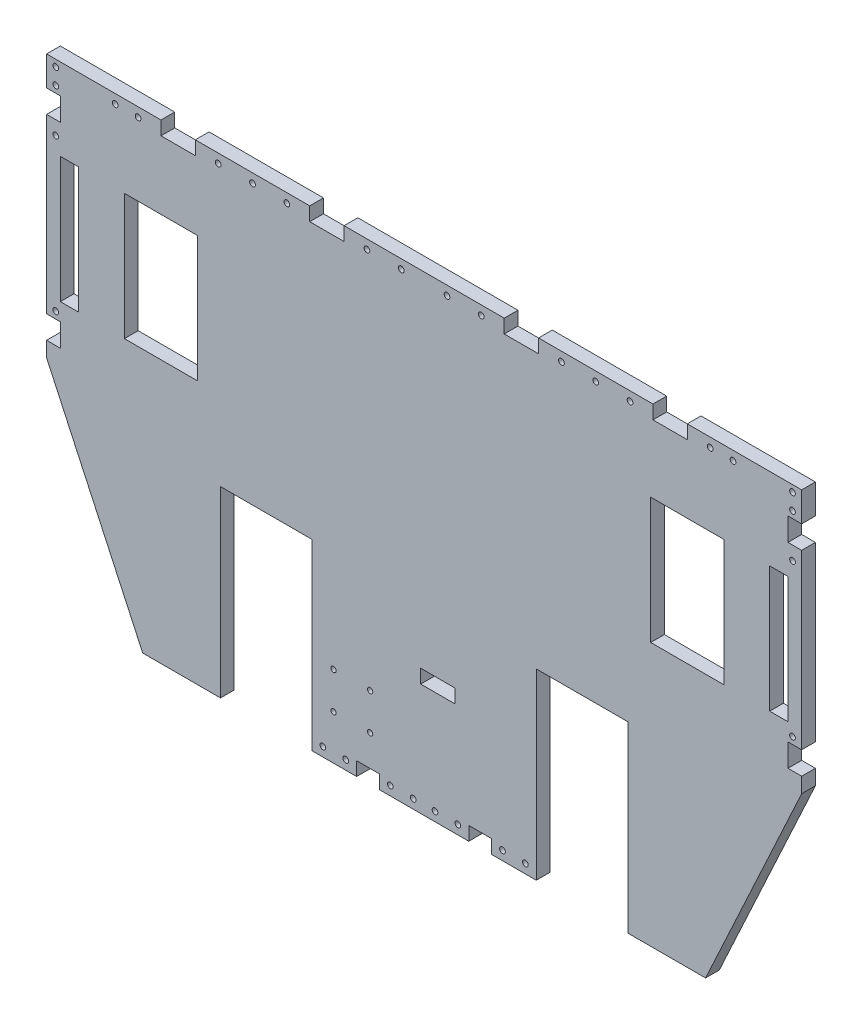
SolidWorks part; units mm, degrees
ref_plane "Plan de face" through (0, 0, 0) normal (0, 0, 1) x (1, 0, 0)
ref_plane "Plan de dessus" through (0, 0, 0) normal (0, 1, 0) x (1, 0, 0)
ref_plane "Plan de droite" through (0, 0, 0) normal (1, 0, 0) x (0, 0, -1)
sketch "Esquisse1" plane through (0, 0, 0) normal (0, 0, 1) x (1, 0, 0)
  line L0 (0, 124.9429) -> (0, -204.46) construction
  line L1 (-165, 96.73) -> (165, 96.73)
  line L2 (165, 96.73) -> (165, -18.27)
  line L3 (165, -18.27) -> (123, -109.0224)
  line L4 (123, -109.0224) -> (-123, -109.0224)
  line L5 (-211.9802, 0) -> (248.5953, 0) construction
  line L6 (-123, -109.0224) -> (-165, -18.27)
  line L7 (-165, -18.27) -> (-165, 96.73)
  line L9 (13.5, -54.0224) -> (-1.5, -54.0224)
  line L10 (13.5, -54.0224) -> (13.5, -60.0224)
  line L11 (13.5, -60.0224) -> (-1.5, -60.0224)
  line L12 (-1.5, -54.0224) -> (-1.5, -60.0224)
  circle A0 centre (-23.6, -89.5224) radius 1.15
  circle A1 centre (-23.6, -73.5224) radius 1.15
  circle A2 centre (-39.6, -89.5224) radius 1.15
  circle A3 centre (-39.6, -73.5224) radius 1.15
  dimension "D15" = 2.3
  dimension "D16" = 2.3
  dimension "D17" = 2.3
  dimension "D18" = 2.3
  dimension "D24" = 83.4
  dimension "D2" = 165
  dimension "D3" = 330
  dimension "D4" = 100
  dimension "D5" = 115
  dimension "D6" = 100
  dimension "D7" = 246
  dimension "D8" = 205.7524
  dimension "D9" = 96.73
  dimension "D10" = 115
  dimension "D11" = 6
  dimension "D12" = 15
  dimension "D13" = 49
  dimension "D14" = 109.5
  dimension "D19" = 19.5
  dimension "D20" = 16
  dimension "D21" = 16
  dimension "D22" = 16
  dimension "D23" = 16
extrude "Boss.-Extru.1" add sketch "Esquisse1" along normal blind 6
sketch "Esquisse2" plane through (0, 0, 6) normal (0, 0, 1) x (1, 0, 0)
  line L0 (-123, -109.0224) -> (123, -109.0224) construction
  line L1 (-159, 60.9776) -> (-151, 60.9776)
  line L2 (-159, 60.9776) -> (-159, 5.9776)
  line L3 (-159, 5.9776) -> (-151, 5.9776)
  line L4 (-151, 60.9776) -> (-151, 5.9776)
  line L5 (-131, 60.9776) -> (-99, 60.9776)
  line L6 (-131, 60.9776) -> (-131, 5.9776)
  line L7 (-131, 5.9776) -> (-99, 5.9776)
  line L8 (-99, 60.9776) -> (-99, 5.9776)
  line L9 (0, 145.0258) -> (0, -189.2208) construction
  line L10 (99, 60.9776) -> (99, 5.9776)
  line L11 (131, 5.9776) -> (99, 5.9776)
  line L12 (131, 60.9776) -> (131, 5.9776)
  line L13 (131, 60.9776) -> (99, 60.9776)
  line L14 (151, 60.9776) -> (151, 5.9776)
  line L15 (159, 5.9776) -> (151, 5.9776)
  line L16 (159, 60.9776) -> (159, 5.9776)
  line L17 (159, 60.9776) -> (151, 60.9776)
  line L19 (89, -109.0224) -> (89, -29.0224)
  line L20 (-49, -109.0224) -> (-89, -109.0224)
  line L21 (-49, -109.0224) -> (-49, -29.0224)
  line L22 (-49, -29.0224) -> (-89, -29.0224)
  line L23 (-89, -109.0224) -> (-89, -29.0224)
  line L24 (49, -29.0224) -> (89, -29.0224)
  line L25 (49, -109.0224) -> (49, -29.0224)
  line L26 (49, -109.0224) -> (89, -109.0224)
  line L27 (-165, 96.73) -> (-165, -18.27) construction
  line L28 (-123, -109.0224) -> (123, -109.0224) construction
  dimension "D2" = 8
  dimension "D3" = 20
  dimension "D4" = 32
  dimension "D5" = 99
  dimension "D6" = 55
  dimension "D7" = 55
  dimension "D8" = 115
  dimension "D9" = 115
  dimension "D10" = 40
  dimension "D11" = 80
  dimension "D12" = 76
  dimension "D13" = 98
  dimension "D14" = 6
  dimension "D15" = 0
extrude "Enlèv. mat.-Extru.1" cut sketch "Esquisse2" against normal blind 6
sketch "Esquisse3" plane through (0, 0, 0) normal (0, 0, -1) x (-1, 0, 0)
  line L0 (165, 96.73) -> (165, -18.27) construction
  line L1 (165, -11.645) -> (159, -11.645)
  line L2 (165, -11.645) -> (165, -1.645)
  line L3 (165, -1.645) -> (159, -1.645)
  line L4 (159, -11.645) -> (159, -1.645)
  line L5 (49, -109.0224) -> (-49, -109.0224) construction
  line L6 (165, 73.8526) -> (159, 73.8526)
  line L7 (165, 73.8526) -> (165, 83.8526)
  line L8 (165, 83.8526) -> (159, 83.8526)
  line L9 (159, 73.8526) -> (159, 83.8526)
  line L10 (29.5, -109.0224) -> (19.5, -109.0224)
  line L11 (29.5, -109.0224) -> (29.5, -103.0224)
  line L12 (29.5, -103.0224) -> (19.5, -103.0224)
  line L13 (19.5, -109.0224) -> (19.5, -103.0224)
  line L14 (49, -109.0224) -> (49, -29.0224) construction
  line L15 (0, -209.4812) -> (0, 177.1799) construction
  line L17 (151, 60.9776) -> (159, 60.9776) construction
  line L18 (-19.5, -109.0224) -> (-19.5, -103.0224)
  line L19 (-29.5, -103.0224) -> (-19.5, -103.0224)
  line L20 (-29.5, -109.0224) -> (-29.5, -103.0224)
  line L21 (-29.5, -109.0224) -> (-19.5, -109.0224)
  line L22 (-159, 73.8526) -> (-159, 83.8526)
  line L23 (-165, 83.8526) -> (-159, 83.8526)
  line L24 (-165, 73.8526) -> (-165, 83.8526)
  line L25 (-165, 73.8526) -> (-159, 73.8526)
  line L26 (-159, -11.645) -> (-159, -1.645)
  line L27 (-165, -1.645) -> (-159, -1.645)
  line L28 (-165, -11.645) -> (-165, -1.645)
  line L29 (-165, -11.645) -> (-159, -11.645)
  line L30 (-165, 96.73) -> (165, 96.73) construction
  line L31 (115, 96.73) -> (100, 96.73)
  line L32 (115, 96.73) -> (115, 90.73)
  line L33 (115, 90.73) -> (100, 90.73)
  line L34 (100, 96.73) -> (100, 90.73)
  line L35 (-35, 96.73) -> (-35, 90.73)
  line L36 (50, 96.73) -> (35, 96.73)
  line L37 (50, 96.73) -> (50, 90.73)
  line L38 (50, 90.73) -> (35, 90.73)
  line L39 (35, 96.73) -> (35, 90.73)
  line L40 (-50, 90.73) -> (-35, 90.73)
  line L41 (-50, 96.73) -> (-50, 90.73)
  line L42 (-50, 96.73) -> (-35, 96.73)
  line L43 (-100, 96.73) -> (-100, 90.73)
  line L44 (-115, 90.73) -> (-100, 90.73)
  line L45 (-115, 96.73) -> (-115, 90.73)
  line L46 (-115, 96.73) -> (-100, 96.73)
  dimension "D1" = 10
  dimension "D2" = 6
  dimension "D3" = 6
  dimension "D4" = 10
  dimension "D5" = 10
  dimension "D6" = 6
  dimension "D7" = 19.5
  dimension "D8" = 6.625
  dimension "D9" = 12.875
  dimension "D10" = 15
  dimension "D11" = 15
  dimension "D12" = 50
  dimension "D13" = 50
  dimension "D14" = 6
extrude "Enlèv. mat.-Extru.2" cut sketch "Esquisse3" against normal blind 6
sketch "Esquisse4" plane through (0, 0, 0) normal (0, 0, -1) x (-1, 0, 0)
  line L0 (159, 73.8526) -> (165, 73.8526) construction
  line L1 (165, 83.8526) -> (159, 83.8526) construction
  line L2 (54.0695, -105.0224) -> (4.75, -105.0224) construction
  line L3 (49, -109.0224) -> (29.5, -109.0224) construction
  line L4 (49, -109.0224) -> (49, -29.0224) construction
  line L5 (19.5, -103.0224) -> (19.5, -109.0224) construction
  line L8 (165, 73.8526) -> (165, -1.645) construction
  line L10 (165, 96.73) -> (165, 83.8526) construction
  line L11 (143.8632, 92.73) -> (10, 92.73) construction
  line L12 (50, 96.73) -> (100, 96.73) construction
  line L13 (115, 90.73) -> (115, 96.73) construction
  line L14 (100, 96.73) -> (100, 90.73) construction
  line L15 (50, 90.73) -> (50, 96.73) construction
  line L16 (35, 96.73) -> (35, 90.73) construction
  line L17 (0, 142.2997) -> (0, -202.2086) construction
  line L18 (-143.8632, 92.73) -> (-10, 92.73) construction
  line L19 (-54.0695, -105.0224) -> (-4.75, -105.0224) construction
  line L21 (165, -1.645) -> (159, -1.645) construction
  circle A0 centre (161, 1.355) radius 1.25
  circle A2 centre (161, 67.8526) radius 1.25
  circle A4 centre (161, 86.8526) radius 1.25
  circle A5 centre (161, 93.8526) radius 1.25
  circle A6 centre (44.25, -105.0224) radius 1.25
  circle A7 centre (14.75, -105.0224) radius 1.25
  circle A8 centre (4.75, -105.0224) radius 1.25
  circle A9 centre (34.2497, -105.0224) radius 1.25
  circle A10 centre (135, 92.73) radius 1.25
  circle A11 centre (125, 92.73) radius 1.25
  circle A12 centre (90, 92.73) radius 1.25
  circle A13 centre (75, 92.73) radius 1.25
  circle A14 centre (60, 92.73) radius 1.25
  circle A15 centre (25, 92.73) radius 1.25
  circle A16 centre (10, 92.73) radius 1.25
  circle A17 centre (-10, 92.73) radius 1.25
  circle A18 centre (-25, 92.73) radius 1.25
  circle A19 centre (-60, 92.73) radius 1.25
  circle A20 centre (-75, 92.73) radius 1.25
  circle A21 centre (-90, 92.73) radius 1.25
  circle A22 centre (-125, 92.73) radius 1.25
  circle A23 centre (-135, 92.73) radius 1.25
  circle A24 centre (-34.2497, -105.0224) radius 1.25
  circle A25 centre (-4.75, -105.0224) radius 1.25
  circle A26 centre (-14.75, -105.0224) radius 1.25
  circle A27 centre (-44.25, -105.0224) radius 1.25
  circle A28 centre (-161, 93.8526) radius 1.25
  circle A29 centre (-161, 86.8526) radius 1.25
  circle A31 centre (-161, 67.8526) radius 1.25
  circle A33 centre (-161, 1.355) radius 1.25
  dimension "D1" = 2.5
  dimension "D2" = 2.5
  dimension "D3" = 2.5
  dimension "D10" = 2.5
  dimension "D11" = 2.5
  dimension "D12" = 2.5
  dimension "D13" = 2.5
  dimension "D14" = 10.0003
  dimension "D18" = 4
  dimension "D19" = 2.5
  dimension "D29" = 2.5
  dimension "D30" = 2.5
  dimension "D31" = 2.5
  dimension "D32" = 2.5
  dimension "D33" = 2.5
  dimension "D34" = 2.5
  dimension "D35" = 2.5
  dimension "D40" = 10
  dimension "D5" = 3
  dimension "D6" = 6
  dimension "D7" = 3
  dimension "D8" = 7
  dimension "D9" = 4
  dimension "D15" = 4.75
  dimension "D16" = 10
  dimension "D17" = 4.75
  dimension "D24" = 4
  dimension "D25" = 4
  dimension "D26" = 4
  dimension "D28" = 4
  dimension "D36" = 10
  dimension "D37" = 10
  dimension "D38" = 10
  dimension "D39" = 15
  dimension "D41" = 15
  dimension "D42" = 10
extrude "Enlèv. mat.-Extru.3" cut sketch "Esquisse4" against normal blind 6
